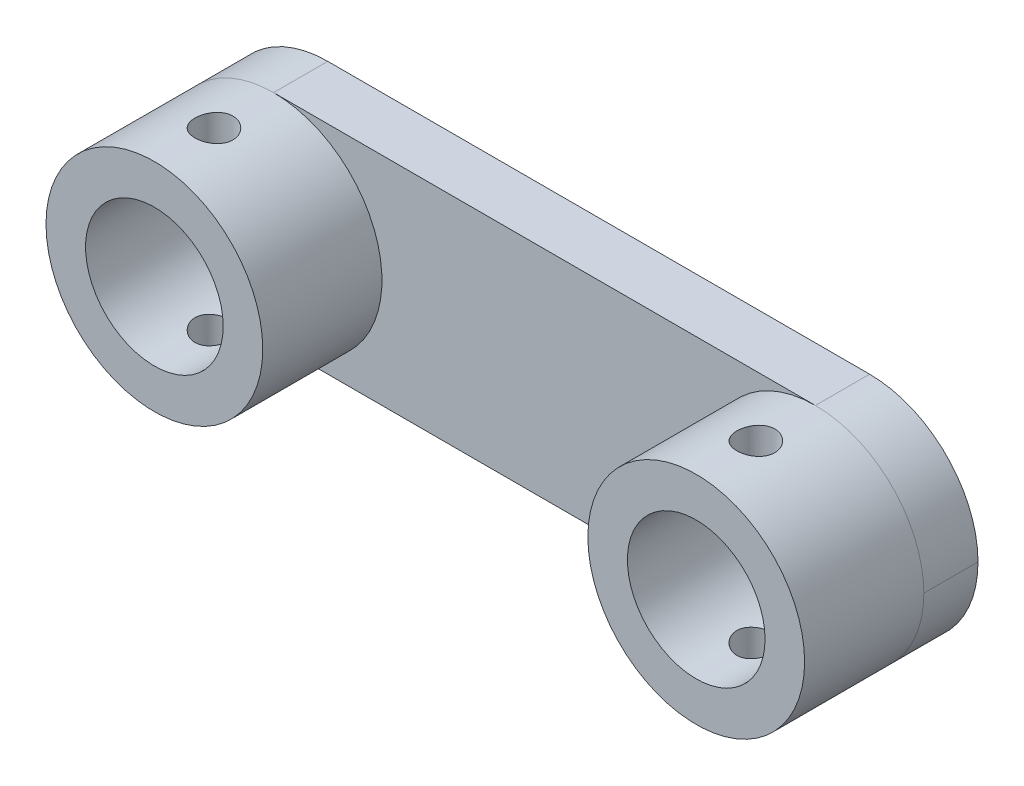
SolidWorks part; units mm, degrees
ref_plane "Front Plane" through (0, 0, 0) normal (0, 0, 1) x (1, 0, 0)
ref_plane "Top Plane" through (0, 0, 0) normal (0, 1, 0) x (1, 0, 0)
ref_plane "Right Plane" through (0, 0, 0) normal (1, 0, 0) x (0, 0, -1)
sketch "Sketch1" plane through (0, 0, 0) normal (0, 0, 1) x (1, 0, 0)
  line L1 (-35, 10) -> (35, 10)
  line L2 (-35, 10) -> (-35, -10)
  line L3 (-35, -10) -> (35, -10)
  line L4 (35, 10) -> (35, -10)
  line L5 (-35, 10) -> (35, -10) construction
  line L6 (-35, -10) -> (35, 10) construction
  point P0 (0, 0)
  dimension "D1" = 20
  dimension "D2" = 70
extrude "Boss-Extrude1" add sketch "Sketch1" along normal blind 5
sketch "Sketch2" plane through (0, 0, 5) normal (0, 0, 1) x (1, 0, 0)
  circle A0 centre (-25, 0) radius 6.35
  circle A1 centre (25, 0) radius 6.35
  circle A2 centre (-25, 0) radius 10
  circle A3 centre (25, 0) radius 10
  dimension "D1" = 12.7
  dimension "D2" = 20
  dimension "D3" = 25
  dimension "D4" = 25
extrude "Boss-Extrude2" add sketch "Sketch2" along normal blind 11
sketch "Sketch3" plane through (0, 10, 0) normal (0, 1, 0) x (1, 0, 0)
  line L0 (-31.35, -5) -> (-18.65, -5) construction
  circle A0 centre (-25, -10.5) radius 1.75
  circle A1 centre (25, -10.5) radius 1.75
  dimension "D2" = 3.5
  dimension "D1" = 5.5
extrude "Cut-Extrude1" cut sketch "Sketch3" against normal through all
fillet "Fillet1" radius 10 4 edges at (-35, -10, 2.5) (-35, 10, 2.5) (35, 10, 2.5) (35, -10, 2.5)
